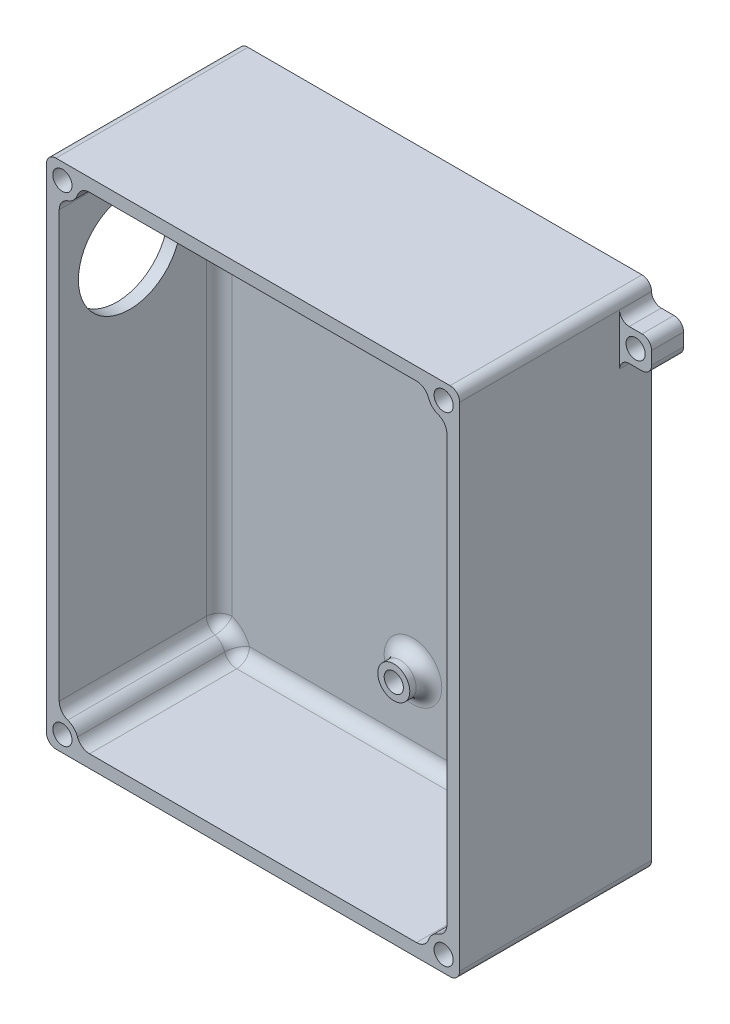
SolidWorks part; units mm, degrees
ref_plane "Front Plane" through (0, 0, 0) normal (0, 0, 1) x (1, 0, 0)
ref_plane "Top Plane" through (0, 0, 0) normal (0, 1, 0) x (1, 0, 0)
ref_plane "Right Plane" through (0, 0, 0) normal (1, 0, 0) x (0, 0, -1)
sketch "Sketch1" plane through (0, 0, 0) normal (0, 0, 1) x (1, 0, 0)
  line L0 (0, 40) -> (0, -40) construction
  line L1 (-32.2923, -40) -> (32.2923, -40)
  line L2 (-32.2923, -40) -> (-32.2923, 40)
  line L3 (-32.2923, 40) -> (32.2923, 40)
  line L4 (32.2923, -40) -> (32.2923, 40)
  line L5 (-32.2923, -40) -> (32.2923, 40) construction
  line L6 (-32.2923, 40) -> (32.2923, -40) construction
  line L7 (-34.7923, -32) -> (-34.7923, -37) construction
  line L8 (32.2923, 37) -> (37.2923, 37)
  line L9 (32.2923, 37) -> (32.2923, 32)
  line L10 (32.2923, 32) -> (37.2923, 32)
  line L11 (37.2923, 37) -> (37.2923, 32)
  line L12 (-32.2923, -37) -> (-37.2923, -37)
  line L13 (-32.2923, -37) -> (-32.2923, -32)
  line L14 (-32.2923, -32) -> (-37.2923, -32)
  line L15 (-37.2923, -37) -> (-37.2923, -32)
  line L16 (-37.2923, -34.5) -> (-32.2923, -34.5) construction
  line L17 (34.7923, 37) -> (34.7923, 32) construction
  line L18 (37.2923, 34.5) -> (32.2923, 34.5) construction
  line L19 (-30.2923, 38) -> (30.2923, 38)
  line L20 (30.2923, -38) -> (30.2923, 38)
  line L21 (-30.2923, -38) -> (30.2923, -38)
  line L22 (-30.2923, -38) -> (-30.2923, 38)
  line L23 (-32.2923, 0) -> (32.2923, 0) construction
  circle A0 centre (0, 26.543) radius 1.5
  circle A1 centre (0, -26.543) radius 1.5
  circle A2 centre (34.7923, 34.5) radius 1.5
  circle A3 centre (-34.7923, -34.5) radius 1.5
  circle A4 centre (-29.7923, 37.5) radius 2.5
  circle A5 centre (29.7923, 37.5) radius 2.5
  circle A6 centre (29.7923, -37.5) radius 2.5
  circle A7 centre (-29.7923, -37.5) radius 2.5
  circle A8 centre (-29.7923, -37.5) radius 1.5
  circle A9 centre (29.7923, -37.5) radius 1.5
  circle A10 centre (-29.7923, 37.5) radius 1.5
  circle A11 centre (29.7923, 37.5) radius 1.5
  circle A12 centre (0, 26.543) radius 2.5
  circle A13 centre (0, -26.543) radius 2.5
  point P0 (0, 0)
  dimension "D5" = 3
  dimension "D7" = 3
  dimension "D12" = 5
  dimension "D1" = 64.5846
  dimension "D2" = 80
  dimension "D3" = 53.086
  dimension "D6" = 5
  dimension "D8" = 3
  dimension "D9" = 3
  dimension "D4" = 13.457
  dimension "D10" = 2
  dimension "D11" = 1
  dimension "D13" = 1
extrude "BASE" add sketch "Sketch1" along normal blind 5 contours A4 L3 L2 | A10 L19 A4 L22 | L19 A5 L3 A4 | L2 A7 L22 A4 | A10 L22 A4 L19 | L21 A8 L22 A7 | L1 A7 L2 | L22 A8 L21 A7 | L21 A7 L1 A6 | A9 L21 A6 L20 | A6 L1 L4 | A6 L4 A5 L20 | A9 L20 A6 L21 | L22 A7 L21 A6 L20 A5 L19 A4 A1 A0 | A0 | A1 | L3 A5 L4 | L19 A11 L20 A5 | L20 A11 L19 A5 | L11 L8 L4 L10 A2 | L15 L12 L2 L14 A3 | L19 A10 L22 | A11 L19 L20 | L21 A9 L20 | L20 A9 L21 | A11 L20 L19 | L22 A10 L19 | A8 L22 L21 | A8 L21 L22 | A12 A0 | A13 A1 region at (-31.7339, -39.4416, 0) region at (0, -39.0108, 0) region at (-31.5106, -39.2183, 0) region at (-31.3007, 0, 0) region at (31.7339, -39.4416, 0) region at (28.2554, -39.3823, 0) region at (0, 0, 0) region at (-28.5989, -36.3066, 0) region at (-34.7923, -36.9293, 0) region at (28.5989, -36.3066, 0) region at (31.3007, 0, 0) region at (-30.8238, -38.5315, 0) region at (-29.3847, -37.0924, 0) region at (-31.6746, 35.9631, 0) region at (-28.5989, 36.3066, 0) region at (29.3847, -37.0924, 0) region at (29.3352, -38.0412, 0) region at (32.363, 34.5, 0) region at (-31.7339, 39.4416, 0) region at (-30.8238, 38.5315, 0) region at (-29.3847, 37.0924, 0) region at (28.5989, 36.3066, 0) region at (30.3623, 35.5681, 0) region at (0, 39.0108, 0) region at (29.3847, 37.0924, 0) region at (30.3335, 37.0429, 0) region at (31.7339, 39.4416, 0) region at (0, 26.543, 0) region at (0, -26.543, 0) region at (-2.4293, 26.543, 0) region at (-2.4293, -26.543, 0)
extrude "WALLS" add sketch "Sketch1<3>" along normal blind 25 from surface contours L19 A5 L3 A4 | A10 L19 A4 L22 | A4 L3 L2 | A10 L22 A4 L19 | L2 A7 L22 A4 | L21 A8 L22 A7 | L22 A8 L21 A7 | L1 A7 L2 | L21 A7 L1 A6 | A9 L20 A6 L21 | A9 L21 A6 L20 | A6 L1 L4 | A6 L4 A5 L20 | L19 A11 L20 A5 | L20 A11 L19 A5 | L3 A5 L4 region at (-31.7339, -39.4416, 0) region at (0, -39.0108, 0) region at (-31.5106, -39.2183, 0) region at (-31.3007, 0, 0) region at (31.7339, -39.4416, 0) region at (28.2554, -39.3823, 0) region at (-28.5989, -36.3066, 0) region at (28.5989, -36.3066, 0) region at (31.3007, 0, 0) region at (-31.6746, 35.9631, 0) region at (-28.5989, 36.3066, 0) region at (-31.7339, 39.4416, 0) region at (28.5989, 36.3066, 0) region at (30.3623, 35.5681, 0) region at (0, 39.0108, 0) region at (31.7339, 39.4416, 0) starting at face at (0, 0, 5)
sketch "Sketch1<3>" plane through (0, 0, 0) normal (0, 0, 1) x (1, 0, 0) same geometry as "Sketch1"
extrude "STANDOFFs" add sketch "Sketch1<5>" along normal blind 3 from surface contours A13 A1 | A12 A0 region at (-2.4293, 26.543, 0) region at (-2.4293, -26.543, 0) starting at face at (0, 0, 5)
sketch "Sketch1<5>" plane through (0, 0, 0) normal (0, 0, 1) x (1, 0, 0) same geometry as "Sketch1"
fillet "External Fillet" radius 1.5 12 edges at (32.2923, 37, 2.5) (37.2923, 37, 2.5) (37.2923, 32, 2.5) (32.2923, 32, 2.5) (-32.2923, -32, 2.5) (-37.2923, -32, 2.5) (-37.2923, -37, 2.5) (-32.2923, -37, 2.5) (32.2923, 40, 15) (32.2923, -40, 15) (-32.2923, -40, 15) (-32.2923, 40, 15)
fillet "Internal Fillet" radius 2 18 edges at (-30.2923, -35.0505, 17.5) (-27.3428, -38, 17.5) (27.3428, -38, 17.5) (30.2923, -35.0505, 17.5) (-30.2923, 35.0505, 17.5) (-27.3428, 38, 17.5) (27.3428, 38, 17.5) (30.2923, 35.0505, 17.5) (-28.0245, -35.7322, 5) (2.5, -26.543, 5) (0, -38, 5) (28.0245, -35.7322, 5) (2.5, 26.543, 5) (-30.2923, 0, 5) (-28.0245, 35.7322, 5) (30.2923, 0, 5) (28.0245, 35.7322, 5) (0, 38, 5)
sketch "Sketch2" plane through (32.2923, 0, 0) normal (1, 0, 0) x (0, 0, -1)
sketch "Sketch3" plane through (-32.2923, 0, 0) normal (-1, 0, 0) x (0, 0, 1)
  line L0 (30, 38.5) -> (30, -38.5) construction
  line L1 (7, 33.2574) -> (30, 33.2574) construction
  circle A0 centre (19, 22.2574) radius 8
  dimension "D1" = 16
  dimension "D2" = 11
  dimension "D3" = 11
extrude "Cut-Extrude2" cut sketch "Sketch3" against normal up to surface (2 mm away) up to face at (-30.2923, 0, 18.5)
equation "\"D9@Sketch1\"=\"D8@Sketch1\""
equation "\"D4@Sketch1\"=(\"D2@Sketch1\"-\"D3@Sketch1\")/2"
equation "\"D2@Sketch3\"=\"D1@Sketch3\"/2 + 3mm"
equation "\"D3@Sketch3\"=\"D2@Sketch3\""
